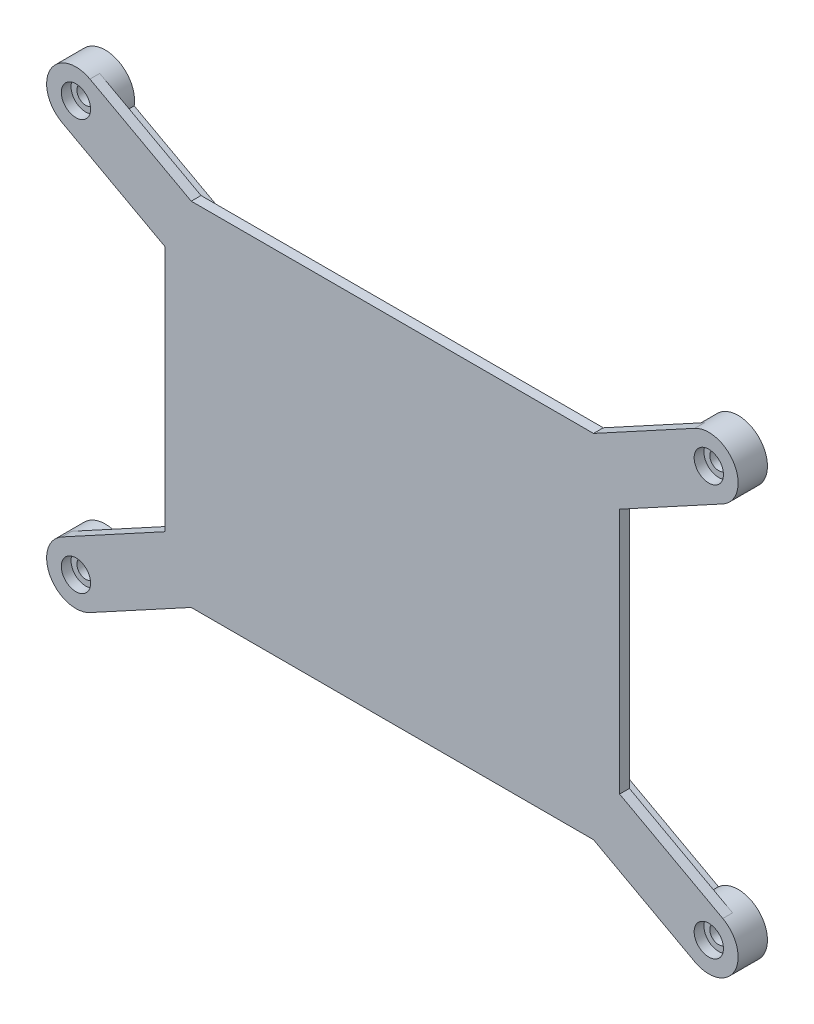
SolidWorks part; units mm, degrees
ref_plane "Front Plane" through (0, 0, 0) normal (0, 0, 1) x (1, 0, 0)
ref_plane "Top Plane" through (0, 0, 0) normal (0, 1, 0) x (1, 0, 0)
ref_plane "Right Plane" through (0, 0, 0) normal (1, 0, 0) x (0, 0, -1)
sketch "Sketch9" plane through (0, 0, 0) normal (0, 0, 1) x (1, 0, 0)
  line L0 (-60.7361, -37.5403) -> (-42.5, -27.6222)
  line L1 (-42.5, -27.6222) -> (-42.5, 27.6222)
  line L2 (-42.5, 27.6222) -> (-60.7361, 37.5403)
  line L3 (-58.825, 41.0542) -> (-38.5, 30)
  line L4 (-38.5, 30) -> (-38.5, -30)
  line L5 (-38.5, -30) -> (-58.825, -41.0542)
  line L6 (-51.6181, -32.5812) -> (-49.7069, -36.0952) construction
  line L7 (-51.6181, 32.5812) -> (-49.7069, 36.0952) construction
  line L8 (51.6181, -32.5812) -> (49.7069, -36.0952) construction
  line L9 (64.75, -42) -> (50.6625, -34.3382) construction
  line L10 (38.5, -30) -> (58.825, -41.0542)
  line L11 (38.5, 30) -> (38.5, -30)
  line L12 (58.825, 41.0542) -> (38.5, 30)
  line L13 (42.5, 27.6222) -> (60.7361, 37.5403)
  line L14 (42.5, -27.6222) -> (42.5, 27.6222)
  line L15 (60.7361, -37.5403) -> (42.5, -27.6222)
  line L16 (-50.6625, 34.3382) -> (-64.75, 42) construction
  line L17 (-50.6625, -34.3382) -> (-64.75, -42) construction
  arc A0 (-60.7361, -37.5403) -> (-58.825, -41.0542) centre (-64.75, -42) ccw
  arc A1 (-58.825, 41.0542) -> (-60.7361, 37.5403) centre (-64.75, 42) ccw
  arc A4 (-58.825, -41.0542) -> (-60.7361, -37.5403) centre (-64.75, -42) ccw construction
  arc A5 (58.825, -41.0542) -> (60.7361, -37.5403) centre (64.75, -42) cw construction
  arc A8 (58.825, 41.0542) -> (60.7361, 37.5403) centre (64.75, 42) cw
  arc A9 (60.7361, -37.5403) -> (58.825, -41.0542) centre (64.75, -42) cw
  point P41 (-38.5, 0)
  dimension "D1" = 12
  dimension "D2" = 4
  dimension "D9" = 129.5
  dimension "D3" = 4
  dimension "D4" = 77
  dimension "D5" = 4
  dimension "D6" = 4
  dimension "D7" = 60
  dimension "D8" = 38.5
  dimension "D10" = 84
extrude "Boss-Extrude4" add sketch "Sketch9" along normal blind 4
sketch "Sketch13" plane through (0, 0, 0) normal (0, 0, 1) x (1, 0, 0)
  line L0 (38.5, 30) -> (38.5, -30) construction
  line L1 (-38.5, -30) -> (38.5, -30)
  line L2 (-38.5, -30) -> (-38.5, -28)
  line L3 (-38.5, -28) -> (38.5, -28)
  line L4 (38.5, -30) -> (38.5, -28)
  dimension "D1" = 2
extrude "Boss-Extrude7" add sketch "Sketch13" against normal blind 2 from surface starting at face at (52.7004, 0, 4)
sketch "Sketch11" plane through (0, 0, 0) normal (0, 1, 0) x (1, 0, 0)
  line L0 (-38.5, -4) -> (-58.825, -4) construction
  line L1 (-38.5, -4) -> (-40.5, -4)
  line L2 (-38.5, -4) -> (-38.5, -1.8)
  line L3 (-38.5, -1.8) -> (-40.5, -1.8)
  line L4 (-40.5, -4) -> (-40.5, -1.8)
  line L5 (-38.5, -4) -> (-38.5, 0) construction
  line L7 (38.5, -4) -> (40.5, -4)
  line L8 (38.5, -4) -> (38.5, -1.8)
  line L9 (38.5, -1.8) -> (40.5, -1.8)
  line L10 (40.5, -4) -> (40.5, -1.8)
  dimension "D1" = 2
  dimension "D2" = 2.2
extrude "Cut-Extrude3" cut sketch "Sketch11" against normal up to surface and the other way up to next up to face at (0, -28, 3)
sketch "Sketch17" plane through (0, -28, 0) normal (0, 1, 0) x (1, 0, 0)
  line L0 (-38.5, 0) -> (-58.825, 0) construction
  line L1 (-38.5, -2) -> (-38.7, -2)
  line L2 (-38.5, -2) -> (-38.5, 0)
  line L3 (-38.5, 0) -> (-38.7, 0)
  line L4 (-38.7, -2) -> (-38.7, 0)
  line L5 (68.7639, 0) -> (38.5, 0) construction
  line L6 (38.5, -2) -> (38.7, -2)
  line L7 (38.5, -2) -> (38.5, 0)
  line L8 (38.5, 0) -> (38.7, 0)
  line L9 (38.7, -2) -> (38.7, 0)
  point P14 (0, 0)
  point P15 (-38.5, -2)
  point P17 (38.5, -2)
  dimension "D1" = 0.2
extrude "Cut-Extrude5" [suppressed] cut sketch "Sketch17" along normal through all both and the other way through all
sketch "Sketch12" plane through (0, 0, 4) normal (0, 0, 1) x (1, 0, 0)
  line L0 (-67.6167, 36.7291) -> (-46.5, 25.2443)
  line L1 (-46.5, 25.2443) -> (-46.5, -25.2443)
  line L2 (-46.5, -25.2443) -> (-67.6167, -36.7291)
  line L3 (-61.8833, -47.2709) -> (-41.16, -36)
  line L4 (-41.16, -36) -> (41.16, -36)
  line L5 (41.16, -36) -> (61.8833, -47.2709)
  line L6 (67.6167, -36.7291) -> (46.5, -25.2443)
  line L7 (46.5, -25.2443) -> (46.5, 25.2443)
  line L8 (46.5, 25.2443) -> (67.6167, 36.7291)
  line L9 (61.8833, 47.2709) -> (41.16, 36)
  line L10 (41.16, 36) -> (-41.16, 36)
  line L11 (-41.16, 36) -> (-61.8833, 47.2709)
  line L12 (-58.825, -41.0542) -> (-38.5, -30) construction
  line L13 (-42.5, -27.6222) -> (-60.7361, -37.5403) construction
  line L14 (-38.5, -30) -> (38.5, -30) construction
  line L16 (58.825, 41.0542) -> (40.5, 31.0877) construction
  line L17 (42.5, 27.6222) -> (60.7361, 37.5403) construction
  line L18 (42.5, -27.6222) -> (42.5, 27.6222) construction
  arc A0 (-61.8833, 47.2709) -> (-67.6167, 36.7291) centre (-64.75, 42) ccw
  arc A1 (-67.6167, -36.7291) -> (-61.8833, -47.2709) centre (-64.75, -42) ccw
  arc A2 (61.8833, -47.2709) -> (67.6167, -36.7291) centre (64.75, -42) ccw
  arc A3 (67.6167, 36.7291) -> (61.8833, 47.2709) centre (64.75, 42) ccw
  arc A4 (60.7361, 37.5403) -> (58.825, 41.0542) centre (64.75, 42) ccw construction
  arc A5 (58.825, -41.0542) -> (60.7361, -37.5403) centre (64.75, -42) ccw construction
  arc A6 (-60.7361, -37.5403) -> (-58.825, -41.0542) centre (-64.75, -42) ccw construction
  arc A7 (-58.825, 41.0542) -> (-60.7361, 37.5403) centre (-64.75, 42) ccw construction
  point P26 (0, 36)
  point P29 (0, -36)
  point P30 (-46.5, 0)
  point P31 (46.5, 0)
  dimension "D1" = 4
  dimension "D2" = 0
  dimension "D3" = 0
  dimension "D4" = 0
  dimension "D5" = 0
  dimension "D6" = 6
extrude "Boss-Extrude6" add sketch "Sketch12" along normal blind 2 contours L10 L11 A0 L0 L1 L2 A1 L3 L4 L5 A2 L6 L7 L8 A3 L9
hole_wizard "M3 Clearance Hole1" positions "Sketch14" profile "Sketch15" hole size "M3" standard "ANSI Metric" end condition through all
sketch "Sketch14" plane through (0, 0, 0) normal (0, 0, -1) x (-1, 0, 0)
  point P0 (64.75, 42)
  point P3 (64.75, -42)
  point P6 (-64.75, -42)
  point P9 (-64.75, 42)
sketch "Sketch15" plane through (-64.75, 42, 0) normal (1, 0, 0) x (0, 1, 0)
  line L0 (0, 0) -> (0, 6)
  line L1 (0, 6) -> (1.8, 6)
  line L2 (1.8, 6) -> (1.8, 0)
  line L5 (1.8, 0) -> (0, 0)
  line L11 (0, -6.35) -> (0, 107.95) construction
  dimension "Thru Hole Dia." = 3.6
  dimension "Thru Hole Depth" = 6
sketch "Sketch16" plane through (0, 0, 6) normal (0, 0, 1) x (1, 0, 0)
  circle A0 centre (-64.75, 42) radius 3
  circle A1 centre (-64.75, -42) radius 3
  circle A2 centre (64.75, -42) radius 3
  circle A3 centre (64.75, 42) radius 3
  dimension "D1" = 6
extrude "Cut-Extrude4" cut sketch "Sketch16" against normal blind 2
chamfer "Chamfer2" distance 2 angle 45 11 edges at (-49.6625, 36.071, 4) (49.6625, 36.071, 4) (51.6181, 32.5812, 4) (42.5, 0, 4) (51.6181, -32.5812, 4) (48.6625, -35.5271, 4) (-48.6625, -35.5271, 4) (-51.6181, -32.5812, 4) (-51.6181, 32.5812, 4) (-42.5, 0, 4) (0, -30, 4)
fillet "Fillet3" [suppressed] radius 4
chamfer "Chamfer3" distance 0.5 angle 45 2 edges at (38.5, 0, 0) (-38.5, 0, 0)
